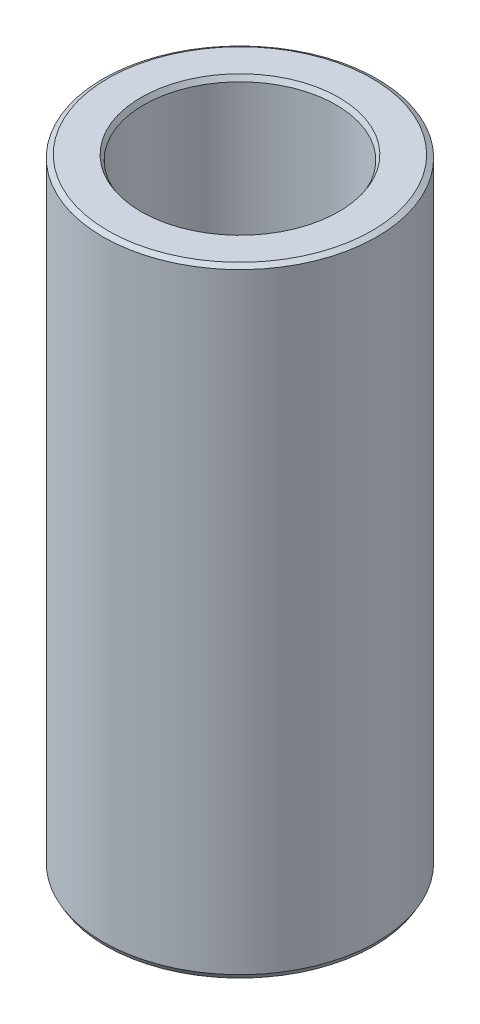
SolidWorks part; units mm, degrees
ref_plane "Front Plane" through (0, 0, 0) normal (0, 0, 1) x (1, 0, 0)
ref_plane "Top Plane" through (0, 0, 0) normal (0, 1, 0) x (1, 0, 0)
ref_plane "Right Plane" through (0, 0, 0) normal (1, 0, 0) x (0, 0, -1)
sketch "Sketch1" plane through (0, 0, 0) normal (0, 1, 0) x (1, 0, 0)
  circle A0 centre (0, 0) radius 42.5
  dimension "SLEEVE_OD" = 85
extrude "Boss-Extrude1" add sketch "Sketch1" along normal blind 191.8943
sketch "Sketch2" plane through (0, 0, 0) normal (0, 1, 0) x (1, 0, 0)
  circle A0 centre (0, 0) radius 29.8148
  dimension "BORE_D" = 59.6295
extrude "Cut-Extrude1" cut sketch "Sketch2" along normal through all
chamfer "Chamfer1" distance 0.8857 angle 60 4 edges at (0, 191.8943, 29.8148) (0, 0, 29.8148) (0, 0, 42.5) (0, 191.8943, 42.5) first distance on face at (0, 191.8943, 29.8148) first distance on face at (0, 0, 29.8148) first distance on face at (0, 191.8943, 42.5)
